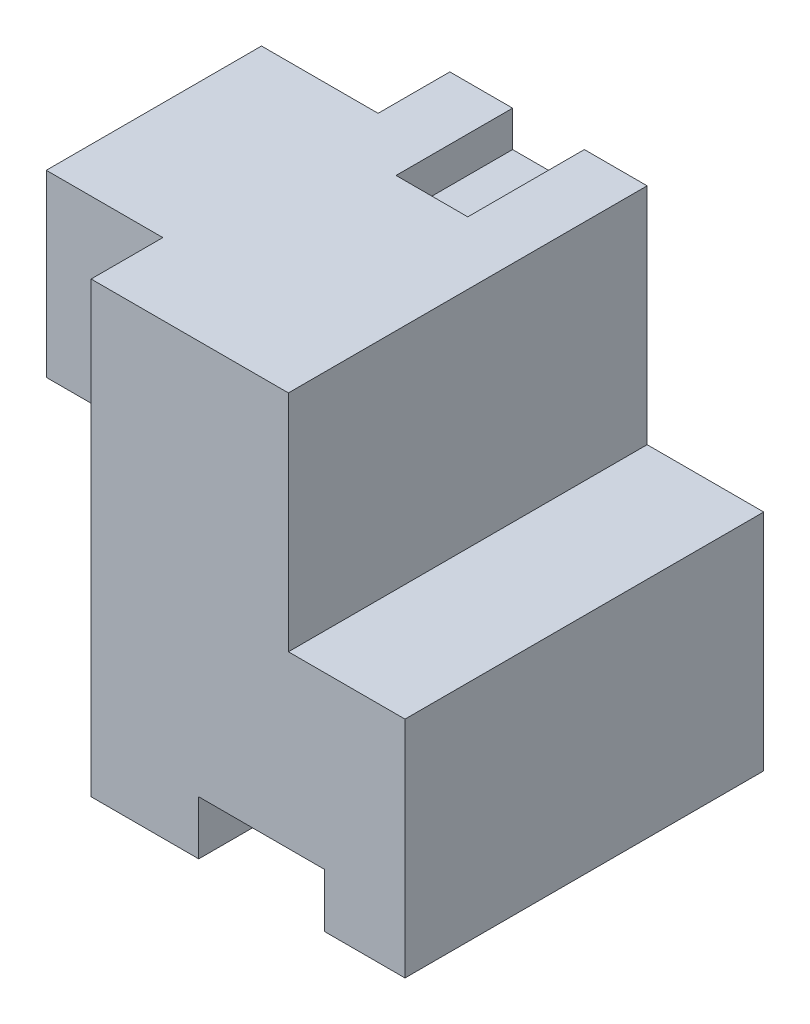
SolidWorks part; units mm, degrees
ref_plane "Спереди" through (0, 0, 0) normal (0, 0, 1) x (1, 0, 0)
ref_plane "Сверху" through (0, 0, 0) normal (0, 1, 0) x (1, 0, 0)
ref_plane "Справа" through (0, 0, 0) normal (1, 0, 0) x (0, 0, -1)
sketch "Эскиз1" plane through (0, 0, 0) normal (0, 0, 1) x (1, 0, 0)
  line L1 (-17.5, -25) -> (17.5, -25)
  line L2 (-17.5, -25) -> (-17.5, 25)
  line L3 (-17.5, 25) -> (17.5, 25)
  line L4 (17.5, -25) -> (17.5, 25)
  line L5 (-17.5, -25) -> (17.5, 25) construction
  line L6 (-17.5, 25) -> (17.5, -25) construction
  line L7 (17.5, 25) -> (4.5, 25)
  line L8 (17.5, 25) -> (17.5, 0)
  line L9 (17.5, 0) -> (4.5, 0)
  line L10 (4.5, 25) -> (4.5, 0)
  line L11 (-17.5, 25) -> (-30.5, 25)
  line L12 (-17.5, 25) -> (-17.5, 5)
  line L13 (-17.5, 5) -> (-30.5, 5)
  line L14 (-30.5, 25) -> (-30.5, 5)
  point P0 (0, 0)
  dimension "D1" = 35
  dimension "D2" = 50
  dimension "D3" = 13
  dimension "D4" = 13
  dimension "D5" = 20
extrude "Бобышка-Вытянуть1" add sketch "Эскиз1" along normal blind 20 and the other way blind 20 contours L10 L3 L2 L1 L4 L9 region at (-2.5088, -2.8509, 0)
extrude "Бобышка-Вытянуть2" add sketch "Эскиз1<3>" along normal offset from surface 8 and the other way offset from surface 8 contours L11 L14 L13 L2 region at (-24, 15, 0) up to face at (1.5, 0, 20) other way up to face at (1.5, 0, -20)
sketch "Эскиз1<3>" plane through (0, 0, 0) normal (0, 0, 1) x (1, 0, 0) same geometry as "Эскиз1"
sketch "Эскиз2" plane through (0, 0, 20) normal (0, 0, 1) x (1, 0, 0)
  line L0 (-17.5, -25) -> (17.5, -25) construction
  line L1 (-5.5, -25) -> (8.5, -25)
  line L2 (-5.5, -25) -> (-5.5, -19)
  line L3 (-5.5, -19) -> (8.5, -19)
  line L4 (8.5, -25) -> (8.5, -19)
  line L5 (-17.5, -25) -> (-17.5, 25) construction
  dimension "D1" = 6
  dimension "D2" = 14
  dimension "D3" = 12
extrude "Вырез-Вытянуть1" cut sketch "Эскиз2" against normal blind 8
sketch "Эскиз3" plane through (0, 25, 0) normal (0, 1, 0) x (1, 0, 0)
  line L0 (-6.5, 20) -> (-6.5, -20) construction
  line L1 (-17.5, 20) -> (4.5, 20) construction
  line L2 (-17.5, -20) -> (4.5, -20) construction
  line L4 (-10.5, 7) -> (-2.5, 7)
  line L5 (-10.5, 7) -> (-10.5, 20)
  line L6 (-10.5, 20) -> (-2.5, 20)
  line L7 (-2.5, 7) -> (-2.5, 20)
  line L8 (-10.5, 7) -> (-2.5, 20) construction
  line L9 (-10.5, 20) -> (-2.5, 7) construction
  point P6 (-6.5, 13.5)
  dimension "D1" = 8
  dimension "D2" = 13
extrude "Вырез-Вытянуть2" cut sketch "Эскиз3" against normal blind 4
